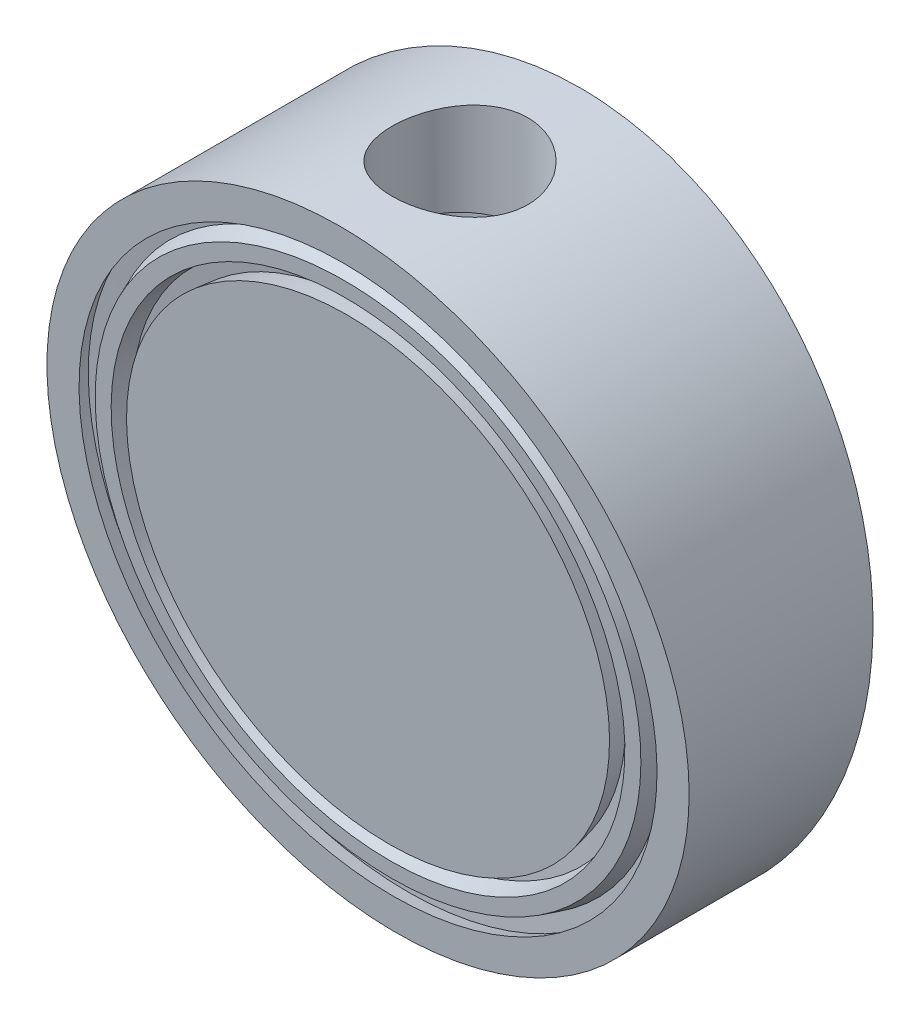
SolidWorks part; units mm, degrees
ref_plane "Front Plane" through (0, 0, 0) normal (0, 0, 1) x (1, 0, 0)
ref_plane "Top Plane" through (0, 0, 0) normal (0, 1, 0) x (1, 0, 0)
ref_plane "Right Plane" through (0, 0, 0) normal (1, 0, 0) x (0, 0, -1)
sketch "Sketch1" plane through (0, 0, 0) normal (1, 0, 0) x (0, 0, -1)
  line L0 (0, 0) -> (0, 63.5) construction
  line L1 (-23.8125, 63.5) -> (23.8125, 63.5)
  line L2 (23.8125, 63.5) -> (23.8125, 0)
  line L3 (-23.8125, 0) -> (23.8125, 0) construction
  line L4 (-23.8125, 63.5) -> (-23.8125, 0)
  line L5 (-23.8125, 0) -> (23.8125, 0)
  dimension "D1" = 23.8125
  dimension "D2" = 63.5
revolve "Revolve1" add sketch "Sketch1" angle 360 about L5
sketch "Sketch2" plane through (0, 0, 0) normal (1, 0, 0) x (0, 0, -1)
  line L0 (-23.8125, 63.5) -> (-12.7, -63.5)
  line L1 (-23.8125, -63.5) -> (23.8125, -63.5) construction
  line L2 (-12.7, -63.5) -> (0, -63.5)
  line L4 (23.8125, 63.5) -> (-23.8125, 63.5) construction
  line L5 (0, 63.5) -> (0, -63.5) construction
  line L6 (-23.8125, 63.5) -> (-23.8125, -63.5) construction
  line L7 (-23.8125, -63.5) -> (23.8125, -63.5)
  line L8 (-23.8125, 63.5) -> (-23.8125, -63.5)
  line L9 (23.8125, 63.5) -> (23.8125, -63.5)
  line L10 (23.8125, 63.5) -> (12.7, -63.5)
  dimension "D1" = 12.7
extrude "Cut-Extrude1" cut sketch "Sketch2" against normal up to surface and the other way up to surface contours L0 L8 L7 | L9 L10 L7 region at (0, -21.1667, -20.1083) region at (0, -21.1667, 20.1083) up to face at (63.5, 0, 23.8125) other way up to face at (63.5, 0, 23.8125)
sketch "Sketch3" plane through (0, 0, 0) normal (1, 0, 0) x (0, 0, -1)
  line L0 (-18.2562, 0) -> (0, 1.5974) construction
  line L1 (-23.8125, 63.5) -> (-12.7, -63.5) construction
  line L2 (-13.2747, -56.9325) -> (-10.2888, -57.7325)
  line L3 (-10.2888, -57.7325) -> (-10.2888, -54.632)
  line L4 (-10.2888, -54.632) -> (-13.5525, -53.7575)
  line L5 (-13.8282, -50.6066) -> (-10.2888, -49.6583)
  line L6 (-10.2888, -49.6583) -> (-10.2888, -46.5577)
  line L7 (-10.2888, -46.5577) -> (-14.0933, -47.5771)
  line L9 (-13.6936, -52.1451) -> (13.6936, -52.1451) construction
  line L11 (12.7, -63.5) -> (23.8125, 63.5) construction
  line L12 (-10.2888, -49.6583) -> (-10.2888, -54.632) construction
  line L13 (0, 1.5974) -> (0, -52.1451) construction
  line L14 (10.2888, -49.6583) -> (10.2888, -54.632) construction
  line L15 (18.2562, 0) -> (0, 1.5974) construction
  line L16 (10.2888, -46.5577) -> (14.0933, -47.5771)
  line L17 (10.2888, -49.6583) -> (10.2888, -46.5577)
  line L18 (13.8282, -50.6066) -> (10.2888, -49.6583)
  line L19 (10.2888, -54.632) -> (13.5525, -53.7575)
  line L20 (10.2888, -57.7325) -> (10.2888, -54.632)
  line L21 (13.2747, -56.9325) -> (10.2888, -57.7325)
  line L22 (12.7, -63.5) -> (23.8125, 63.5)
  line L23 (-23.8125, 63.5) -> (-12.7, -63.5)
  point P11 (-10.2888, -52.1451)
  dimension "D1" = 15
  dimension "D2" = 15
  dimension "D3" = 3.175
  dimension "D4" = 3.175
  dimension "D5" = 57.15
  dimension "D6" = 50.8
revolve "Cut-Revolve1" cut sketch "Sketch3" angle 360 about L0 region at (0, -55.7404, 11.8522) region at (0, -48.5815, 12.1256)
revolve "Cut-Revolve2" cut sketch "Sketch3<4>" angle 360 about L15 region at (0, -55.7404, -11.8522) region at (0, -48.5815, -12.1256)
sketch "Sketch3<4>" plane through (0, 0, 0) normal (1, 0, 0) x (0, 0, -1) same geometry as "Sketch3"
sketch "Sketch4" plane through (0, 0, 0) normal (1, 0, 0) x (0, 0, -1)
  line L0 (0, 63.5) -> (0, -63.5) construction
  line L1 (23.8125, 63.5) -> (-23.8125, 63.5) construction
  line L2 (-12.7, -63.5) -> (12.7, -63.5) construction
  line L3 (-6.35, -60.325) -> (-6.35, -46.6674)
  line L4 (-6.35, -46.6674) -> (-7.9375, -45.0799)
  line L5 (-7.9375, -45.0799) -> (-15.6506, 43.0693)
  line L6 (-23.8125, 63.5) -> (-12.7, -63.5) construction
  line L7 (-12.7, -63.5) -> (-9.525, -63.5)
  line L8 (-9.525, -63.5) -> (-6.35, -60.325)
  line L9 (-9.525, -63.5) -> (0, -63.5)
  line L10 (-14.3854, 44.45) -> (-13.4937, 44.45)
  line L11 (-13.4937, 44.45) -> (-13.4937, 76.2)
  line L12 (-13.4937, 76.2) -> (0, 76.2)
  line L13 (0, 76.2) -> (0, 63.5)
  arc A1 (-15.6506, 43.0693) -> (-14.3854, 44.45) centre (-14.3854, 43.18) cw
  point P6 (-6.35, -63.5)
  dimension "D10" = 1.27
  dimension "D1" = 6.35
  dimension "D2" = 6.35
  dimension "D3" = 3.175
  dimension "D4" = 45
  dimension "D5" = 45
  dimension "D6" = 1.5875
  dimension "D7" = 31.75
  dimension "D8" = 13.4937
  dimension "D9" = 76.2
revolve "Cut-Revolve3" cut sketch "Sketch4" angle 360 about L0 region at (0, 14.8842, 6.0902)
equation "\"hzj\"=1.74046"
